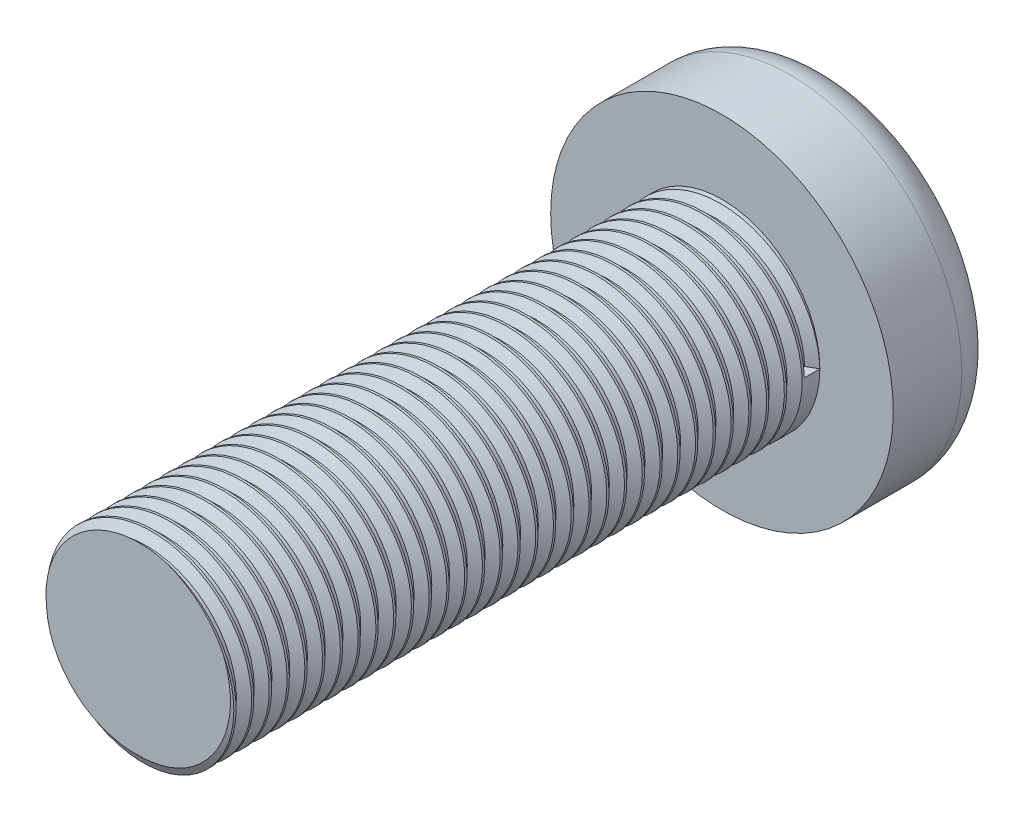
SolidWorks part; units mm, degrees
ref_plane "前视基准面" through (0, 0, 0) normal (0, 0, 1) x (1, 0, 0)
ref_plane "上视基准面" through (0, 0, 0) normal (0, 1, 0) x (1, 0, 0)
ref_plane "右视基准面" through (0, 0, 0) normal (1, 0, 0) x (0, 0, -1)
sketch "草图1" plane through (0, 0, 0) normal (0, 0, 1) x (1, 0, 0)
  circle A0 centre (0, 0) radius 5
extrude "凸台-拉伸1" add sketch "草图1" along normal blind 30 contours A0
sketch "草图2" plane through (0, 0, 0) normal (0, 0, -1) x (-1, 0, 0)
  circle A0 centre (0, 0) radius 8.75
  dimension "D1" = 17.5
extrude "凸台-拉伸2" add sketch "草图2" along normal blind 5.5
fillet "圆角2" radius 2 1 edges at (-8.75, 0, -5.5)
thread "螺纹线1" pitch 0.9071 profile "螺纹线轮廓2" start angle 0, offset 0, length 30, pitch 0.9071, diameter 10
ref_plane "基准面2" through (5, 0, 0) normal (0, -1, 0) x (1, 0, 0)
sketch "螺纹线轮廓2" plane through (5, 0, 0) normal (0, -1, 0) x (1, 0, 0)
  line L0 (0, 0) -> (0, 0.9071) construction
  line L11 (0, 0) -> (0, 0.7937)
  line L12 (0, 0.7937) -> (-0.491, 0.5103)
  line L13 (-0.491, 0.5103) -> (-0.491, 0.2835)
  line L15 (-0.491, 0.2835) -> (0, 0)
  line L17 (-0.491, 0.3969) -> (0, 0.3969) construction
  point P2 (0, 0)
  dimension "Pitch" = 0.9071
  dimension "Profile_Angle" = 60
  dimension "Profile_Land" = 0.2268
  dimension "Profile_Height" = 0.491
